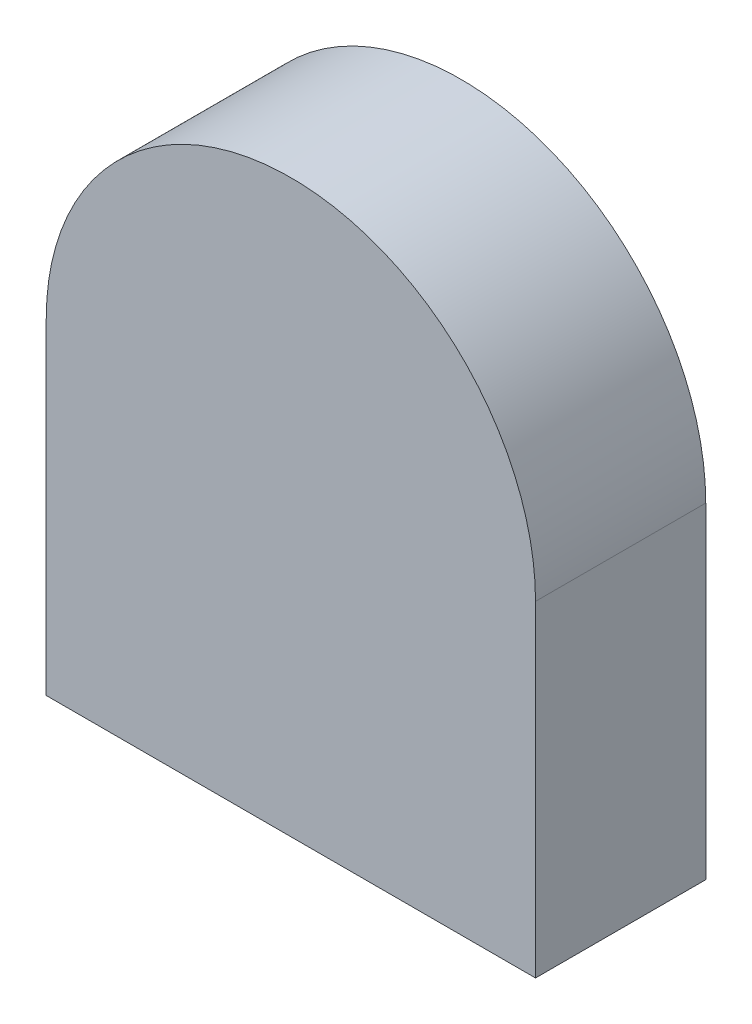
SolidWorks part; units mm, degrees
ref_plane "Front Plane" through (0, 0, 0) normal (0, 0, 1) x (1, 0, 0)
ref_plane "Top Plane" through (0, 0, 0) normal (0, 1, 0) x (1, 0, 0)
ref_plane "Right Plane" through (0, 0, 0) normal (1, 0, 0) x (0, 0, -1)
sketch "Sketch1" plane through (0, 0, 55.0983) normal (0, 0, 1) x (1, 0, 0)
  line L0 (15.5026, 29.7613) -> (15.5026, 15.7613)
  line L1 (1.5026, 15.7613) -> (25.5026, 15.7613) construction
  line L2 (15.5026, 15.7613) -> (35.5026, 15.7613)
  line L3 (35.5026, 15.7613) -> (35.5026, 29.7613)
  line L4 (13.5026, 29.7613) -> (13.5026, 13.7613)
  line L5 (13.5026, 13.7613) -> (37.5026, 13.7613)
  line L6 (37.5026, 13.7613) -> (37.5026, 29.7613)
  arc A0 (35.5026, 29.7613) -> (15.5026, 29.7613) centre (25.5026, 29.7613) ccw
  arc A1 (37.5026, 29.7613) -> (13.5026, 29.7613) centre (25.5026, 29.7613) ccw
  circle M1 centre (25.5026, 29.7613) radius 8.5
  dimension "D1" = 20
  dimension "D2" = 2
extrude "Boss-Extrude1" add sketch "Sketch1" along normal blind 1 contours M1 | L3 A0 L0 L2 M1 | L6 A1 L4 L5 A0 L3 L2 L0 region at (25.5026, 39.4489, 55.0983) region at (25.5026, 41.3925, 55.0983) region at (25.5026, 29.7613, 55.0983)
extrude "Boss-Extrude2" add sketch "Sketch1<4>" against normal up to surface (7.35 mm away)
sketch "Sketch1<4>" plane through (0, 0, 55.0983) normal (0, 0, 1) x (1, 0, 0) same geometry as "Sketch1"
